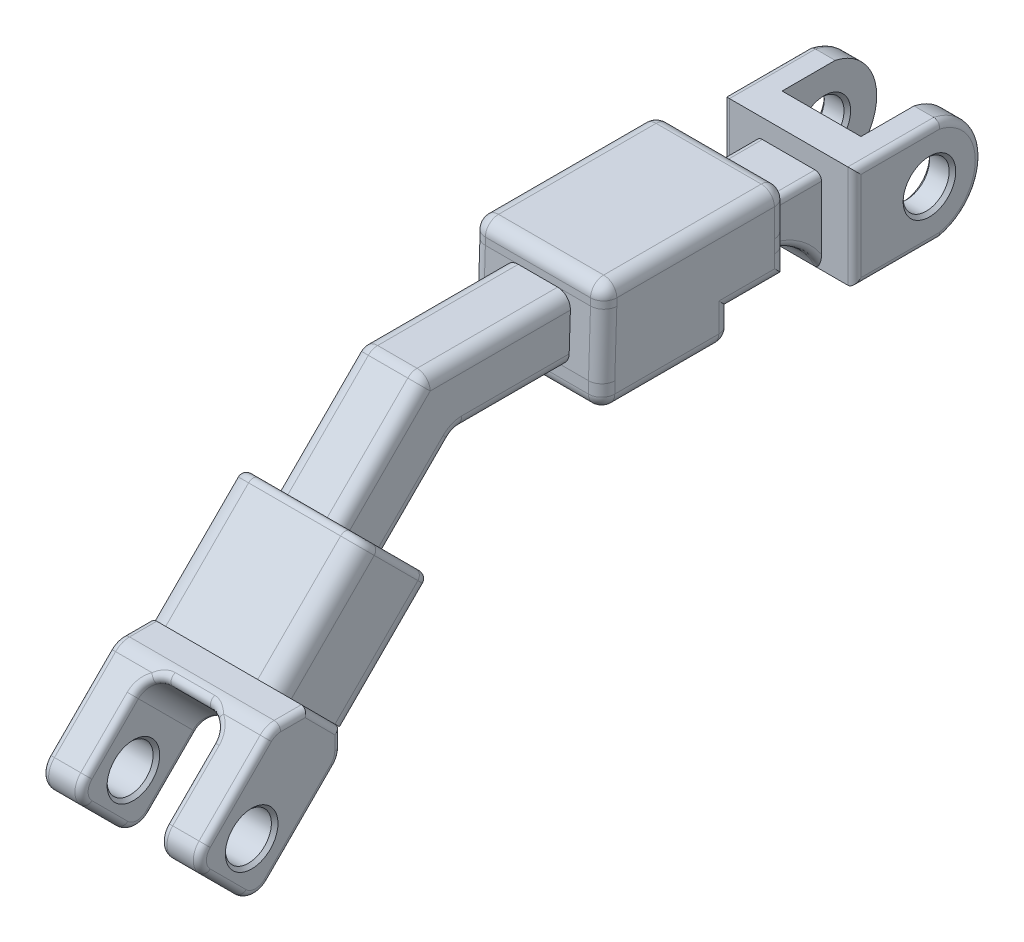
SolidWorks part; units mm, degrees
material "ABS"
ref_plane "Alzado" through (0, 0, 0) normal (0, 0, 1) x (1, 0, 0)
ref_plane "Planta" through (0, 0, 0) normal (0, 1, 0) x (1, 0, 0)
ref_plane "Vista lateral" through (0, 0, 0) normal (1, 0, 0) x (0, 0, -1)
sketch "Croquis4" plane through (0, 0, 0) normal (1, 0, 0) x (0, 0, -1)
  line L0 (294.0556, 267.4264) -> (188.8081, 235.4428) construction
  dimension "D1" = 110
sketch "Croquis5" plane through (0, 0, 0) normal (1, 0, 0) x (0, 0, -1)
  line L0 (179.8347, 236.2643) -> (192.1387, 248.5683)
  line L1 (205.7706, 240.3199) -> (219.087, 253.6362)
  line L2 (219.087, 253.6362) -> (216.6986, 256.0246)
  line L3 (216.6986, 256.0246) -> (227.0958, 266.4218)
  line L4 (227.0958, 266.4218) -> (244.2135, 266.4218)
  line L5 (244.2135, 266.4218) -> (244.2135, 262.6525)
  line L6 (244.2135, 262.6525) -> (264.0386, 262.6525)
  line L7 (264.0386, 262.6525) -> (264.0386, 266.9967)
  line L8 (264.0386, 266.9967) -> (272.5471, 266.9967)
  line L9 (272.5471, 266.9967) -> (272.5471, 271.0085)
  line L10 (272.503, 279.1821) -> (244.5251, 279.1821)
  line L11 (244.5251, 279.1821) -> (244.5251, 276.0953)
  line L12 (244.5251, 276.0953) -> (222.3028, 276.0953)
  line L13 (222.3028, 276.0953) -> (209.4654, 263.2578)
  line L14 (209.4654, 263.2578) -> (208.203, 264.5202)
  line L15 (208.203, 264.5202) -> (194.8866, 251.2039)
  line L16 (272.5471, 271.0085) -> (282.6775, 271.0085)
  line L17 (282.6775, 271.0085) -> (282.6775, 260.2579)
  line L18 (282.6775, 260.2579) -> (295.7469, 260.2579)
  line L19 (295.7469, 275.8569) -> (282.6775, 275.8569)
  line L20 (282.6775, 275.8569) -> (282.6775, 272.9671)
  line L21 (282.6775, 272.9671) -> (272.503, 272.9671)
  line L22 (272.503, 272.9671) -> (272.503, 279.1821)
  line L23 (179.8347, 236.2643) -> (189.5274, 226.5716)
  line L24 (189.5274, 226.5716) -> (202.6077, 239.652)
  line L25 (202.6077, 239.652) -> (202.6077, 243.4632)
  line L26 (202.6077, 243.4632) -> (205.7706, 240.3199)
  line L27 (192.1387, 248.5683) -> (197.5222, 248.5683)
  line L28 (197.5222, 248.5683) -> (194.8866, 251.2039)
  arc A0 (295.7469, 260.2579) -> (295.7469, 275.8569) centre (294.0991, 268.0574) ccw
extrude "Saliente-Extruir1" add sketch "Croquis5" along normal blind 20
sketch "Croquis6" plane through (0, 28.2148, 28.2148) normal (0, 0.7071, 0.7071) x (1, 0, 0)
  line L0 (20, 294.2264) -> (0, 294.2264) construction
  line L1 (4, 294.2264) -> (16, 294.2264)
  line L2 (4, 294.2264) -> (4, 310.2264)
  line L3 (4, 310.2264) -> (16, 310.2264)
  line L4 (16, 294.2264) -> (16, 310.2264)
  line L5 (10, 310.2264) -> (10, 294.2264) construction
  line L6 (0, 311.6269) -> (0, 294.2264) construction
  line L7 (20, 311.6269) -> (20, 294.2264) construction
  dimension "D1" = 12
  dimension "D2" = 16
extrude "Cortar-Extruir1" cut sketch "Croquis6" against normal through all
fillet "Redondeo1" radius 3 6 edges at (10, 239.652, -202.6077) (10, 248.5683, -192.1387) (18, 236.2643, -179.8347) (2, 236.2643, -179.8347) (2, 226.5716, -189.5274) (18, 226.5716, -189.5274)
sketch "Croquis7" plane through (20, 0, 0) normal (1, 0, 0) x (0, 0, -1)
  line L0 (209.4654, 263.2578) -> (216.6986, 256.0246)
  line L1 (216.6986, 256.0246) -> (227.0958, 266.4218)
  line L2 (227.0958, 266.4218) -> (244.2135, 266.4218)
  line L3 (244.2135, 266.4218) -> (244.5251, 276.0953)
  line L4 (244.5251, 276.0953) -> (222.3028, 276.0953)
  line L5 (222.3028, 276.0953) -> (209.4654, 263.2578)
extrude "Cortar-Extruir2" cut sketch "Croquis7" against normal blind 5
sketch "Croquis8" plane through (0, 0, 0) normal (-1, 0, 0) x (0, 0, 1)
  line L0 (-244.5251, 276.0953) -> (-244.2135, 266.4218)
  line L1 (-244.2135, 266.4218) -> (-227.0958, 266.4218)
  line L2 (-227.0958, 266.4218) -> (-216.6986, 256.0246)
  line L3 (-216.6986, 256.0246) -> (-209.4654, 263.2578)
  line L4 (-209.4654, 263.2578) -> (-222.3028, 276.0953)
  line L5 (-222.3028, 276.0953) -> (-244.5251, 276.0953)
extrude "Cortar-Extruir3" cut sketch "Croquis8" against normal blind 5
sketch "Croquis9" plane through (20, 0, 0) normal (1, 0, 0) x (0, 0, -1)
  line L0 (272.503, 272.9671) -> (272.5471, 271.0085)
  line L1 (272.5471, 271.0085) -> (282.6775, 271.0085)
  line L2 (282.6775, 271.0085) -> (282.6775, 272.9671)
  line L3 (282.6775, 275.8569) -> (282.6775, 272.9671) construction
  line L4 (282.6775, 272.9671) -> (272.503, 272.9671) construction
  line L5 (282.6775, 272.9671) -> (272.503, 272.9671)
extrude "Cortar-Extruir4" cut sketch "Croquis9" against normal blind 5
sketch "Croquis10" plane through (0, 0, 0) normal (-1, 0, 0) x (0, 0, 1)
  line L0 (-282.6775, 272.9671) -> (-282.6775, 271.0085)
  line L1 (-282.6775, 271.0085) -> (-272.5471, 271.0085)
  line L2 (-272.5471, 271.0085) -> (-272.503, 272.9671)
  line L3 (-272.503, 272.9671) -> (-282.6775, 272.9671)
extrude "Cortar-Extruir5" cut sketch "Croquis10" against normal blind 5
sketch "Croquis11" plane through (0, 275.8569, 0) normal (0, 1, 0) x (1, 0, 0)
  line L0 (10, 287.6775) -> (10, 308.2863) construction
  line L1 (4, 308.2863) -> (16, 308.2863)
  line L2 (4, 308.2863) -> (4, 287.6775)
  line L3 (4, 287.6775) -> (16, 287.6775)
  line L4 (16, 308.2863) -> (16, 287.6775)
  line L5 (0, 295.7469) -> (0, 282.6775) construction
  line L6 (20, 295.7469) -> (20, 282.6775) construction
  line L7 (20, 282.6775) -> (0, 282.6775) construction
  dimension "D1" = 12
  dimension "D2" = 5
  dimension "D3" = 20.6088
extrude "Cortar-Extruir6" cut sketch "Croquis11" against normal through all
fillet "Redondeo2" radius 3 2 edges at (16, 242.7317, -195.9948) (4, 242.7317, -195.9948)
sketch "Croquis12" plane through (15, 0, 0) normal (1, 0, 0) x (0, 0, -1)
  line L2 (272.5471, 266.9967) -> (272.5471, 271.0085)
  line L3 (272.5471, 271.0085) -> (282.6775, 271.0085)
  line L4 (282.6775, 271.0085) -> (282.6775, 260.2579)
  arc A1 (272.5471, 266.9967) -> (282.6775, 260.2579) centre (272.143, 255.4052) cw
  dimension "D1" = 11.5985
extrude "Saliente-Extruir2" add sketch "Croquis12" against normal up to surface (10 mm away) up to face at (5, 271.9878, -277.6013)
fillet "Redondeo4" radius 3 4 edges at (0, 257.8621, -201.5448) (0, 246.9781, -212.4288) (20, 246.9781, -212.4288) (20, 257.8621, -201.5448)
fillet "Redondeo5" radius 2 10 edges at (5, 266.4218, -235.6546) (10, 266.4218, -227.0958) (5, 261.2232, -221.8972) (5, 276.0953, -233.4139) (10, 276.0953, -222.3028) (5, 269.6766, -215.8841) (15, 276.0953, -233.4139) (15, 269.6766, -215.8841) (15, 266.4218, -235.6546) (15, 261.2232, -221.8972)
fillet "Redondeo6" radius 2 24 edges at (10, 279.1821, -272.503) (10, 279.1821, -244.5251) (20, 269.0026, -272.5471) (20, 266.9967, -268.2928) (20, 264.8246, -264.0386) (20, 264.5371, -244.2135) (20, 271.2585, -244.3693) (20, 277.6387, -244.5251) (20, 279.1821, -258.514) (20, 276.0746, -272.503) (20, 271.9878, -272.525) (0, 279.1821, -258.514) (0, 277.6387, -244.5251) (0, 271.2585, -244.3693) (0, 264.5371, -244.2135) (0, 264.8246, -264.0386) (0, 266.9967, -268.2928) (0, 269.0026, -272.5471) (0, 271.9878, -272.525) (0, 276.0746, -272.503) (10, 262.6525, -244.2135) (20, 262.6525, -254.126) (10, 262.6525, -264.0386) (0, 262.6525, -254.126)
sketch "Croquis13" plane through (20, 0, 0) normal (1, 0, 0) x (0, 0, -1)
  line L0 (197.5222, 248.5683) -> (193.3814, 248.5683) construction
  line L1 (191.2601, 247.6896) -> (181.956, 238.3856) construction
  line L2 (181.956, 234.143) -> (187.406, 228.693) construction
  line L3 (191.6487, 228.693) -> (201.729, 238.7733) construction
  line L4 (202.6077, 240.8946) -> (202.6077, 243.4632) construction
  line L5 (197.5222, 248.5683) -> (193.3814, 248.5683)
  line L6 (191.2601, 247.6896) -> (181.956, 238.3856)
  line L7 (181.956, 234.143) -> (187.406, 228.693)
  line L8 (191.6487, 228.693) -> (201.729, 238.7733)
  line L9 (202.6077, 240.8946) -> (202.6077, 243.4632)
  line L10 (202.6077, 243.4632) -> (197.5222, 248.5683)
  arc A0 (193.3814, 248.5683) -> (191.2601, 247.6896) centre (193.3814, 245.5683) ccw construction
  arc A1 (181.956, 238.3856) -> (181.956, 234.143) centre (184.0774, 236.2643) ccw construction
  arc A2 (187.406, 228.693) -> (191.6487, 228.693) centre (189.5274, 230.8143) ccw construction
  arc A3 (201.729, 238.7733) -> (202.6077, 240.8946) centre (199.6077, 240.8946) ccw construction
  arc A4 (193.3814, 248.5683) -> (191.2601, 247.6896) centre (193.3814, 245.5683) ccw
  arc A5 (181.956, 238.3856) -> (181.956, 234.143) centre (184.0774, 236.2643) ccw
  arc A6 (187.406, 228.693) -> (191.6487, 228.693) centre (189.5274, 230.8143) ccw
  arc A7 (201.729, 238.7733) -> (202.6077, 240.8946) centre (199.6077, 240.8946) ccw
extrude "Saliente-Extruir3" add sketch "Croquis13" along normal blind 2
sketch "Croquis14" plane through (0, 0, 0) normal (-1, 0, 0) x (0, 0, 1)
  line L0 (-197.5222, 248.5683) -> (-202.6077, 243.4632)
  line L7 (-210.3243, 262.3989) -> (-216.9656, 255.7576)
  line L8 (-202.6077, 243.4632) -> (-202.6077, 240.8946)
  line L9 (-202.6077, 243.4632) -> (-202.6077, 240.8946)
  line L10 (-197.5222, 248.5683) -> (-197.0079, 249.0825)
  line L11 (-197.0079, 249.0825) -> (-210.3243, 262.3989)
  line L13 (-216.9656, 255.7576) -> (-203.6427, 242.4346)
  line L14 (-203.6427, 242.4346) -> (-202.6077, 243.4632)
  line L18 (-201.729, 238.7733) -> (-191.6487, 228.693)
  line L19 (-201.729, 238.7733) -> (-191.6487, 228.693)
  line L20 (-187.406, 228.693) -> (-181.956, 234.143)
  line L21 (-187.406, 228.693) -> (-181.956, 234.143)
  line L22 (-181.956, 238.3856) -> (-191.2601, 247.6896)
  line L23 (-181.956, 238.3856) -> (-191.2601, 247.6896)
  line L24 (-193.3814, 248.5683) -> (-197.5222, 248.5683)
  line L25 (-193.3814, 248.5683) -> (-197.5222, 248.5683)
  arc A4 (-202.6077, 240.8946) -> (-201.729, 238.7733) centre (-199.6077, 240.8946) ccw
  arc A5 (-202.6077, 240.8946) -> (-201.729, 238.7733) centre (-199.6077, 240.8946) ccw
  arc A6 (-191.6487, 228.693) -> (-187.406, 228.693) centre (-189.5274, 230.8143) ccw
  arc A7 (-191.6487, 228.693) -> (-187.406, 228.693) centre (-189.5274, 230.8143) ccw
  arc A8 (-181.956, 234.143) -> (-181.956, 238.3856) centre (-184.0774, 236.2643) ccw
  arc A9 (-181.956, 234.143) -> (-181.956, 238.3856) centre (-184.0774, 236.2643) ccw
  arc A10 (-191.2601, 247.6896) -> (-193.3814, 248.5683) centre (-193.3814, 245.5683) ccw
  arc A11 (-191.2601, 247.6896) -> (-193.3814, 248.5683) centre (-193.3814, 245.5683) ccw
  dimension "D1" = 0
extrude "Saliente-Extruir4" add sketch "Croquis14" along normal blind 2
fillet "Redondeo7" radius 1 20 edges at (-2, 248.3399, -192.2333) (-2, 243.0376, -186.608) (-2, 236.2643, -181.0774) (-2, 231.418, -184.681) (-2, 227.8143, -189.5274) (-2, 233.7331, -196.6889) (-2, 239.7466, -202.3794) (-2, 242.1789, -202.6077) (-2, 246.0157, -200.065) (-2, 248.5683, -195.4518) (22, 242.1789, -202.6077) (22, 239.7466, -202.3794) (22, 233.7331, -196.6889) (22, 227.8143, -189.5274) (22, 231.418, -184.681) (22, 236.2643, -181.0774) (22, 243.0376, -186.608) (22, 248.3399, -192.2333) (22, 248.5683, -195.4518) (22, 246.0157, -200.065)
fillet "Redondeo8" radius 1 4 edges at (15, 272.9671, -277.5903) (5, 272.9671, -277.5903) (5, 265.0623, -278.5668) (15, 265.0623, -278.5668)
fillet "Redondeo9" radius 1 8 edges at (0, 268.0574, -302.0708) (0, 275.8569, -289.2122) (0, 268.0574, -282.6775) (0, 260.2579, -289.2122) (20, 268.0574, -302.0708) (20, 260.2579, -289.2122) (20, 268.0574, -282.6775) (20, 275.8569, -289.2122)
fillet "Redondeo11" radius 1 16 edges at (4.8787, 246.9567, -190.5271) (10, 247.578, -191.1484) (15.1213, 246.9567, -190.5271) (16, 241.9211, -185.4916) (16, 236.2643, -181.0774) (16, 231.418, -184.681) (16, 227.8143, -189.5274) (16, 232.2285, -195.1842) (15.1213, 237.264, -200.2198) (10, 237.8853, -200.8411) (4.8787, 237.264, -200.2198) (4, 232.2285, -195.1842) (4, 227.8143, -189.5274) (4, 231.418, -184.681) (4, 236.2643, -181.0774) (4, 241.9211, -185.4916)
fillet "Redondeo13" radius 1 8 edges at (19.1213, 263.8989, -208.8243) (20, 259.0782, -213.645) (19.1213, 254.2576, -218.4656) (10, 253.6362, -219.087) (0.8787, 254.2576, -218.4656) (0, 259.0782, -213.645) (0.8787, 263.8989, -208.8243) (10, 264.5202, -208.203)
sketch "Croquis16" plane through (22, 0, 0) normal (1, 0, 0) x (0, 0, -1)
  line L0 (185.3882, 232.1251) -> (195.4875, 242.2245) construction
  line L1 (182.6632, 234.8501) -> (188.1132, 229.4001) construction
  line L2 (191.9672, 246.9825) -> (182.6632, 237.6785) construction
  circle A0 centre (188.9652, 235.7022) radius 3.5
  circle A1 centre (294.0991, 268.0574) radius 3.5
  arc A2 (295.6388, 261.2579) -> (295.6388, 274.8569) centre (294.0991, 268.0574) ccw construction
  dimension "D2" = 7
  dimension "D1" = 110
extrude "Cortar-Extruir7" cut sketch "Croquis16" against normal through all
chamfer "Chaflán1" distance 0.5 angle 45 8 edges at (0, 268.0574, -297.5991) (4, 268.0574, -290.5991) (16, 268.0574, -297.5991) (20, 268.0574, -297.5991) (16, 239.2022, -188.9652) (4, 235.7022, -185.4652) (-2, 235.7022, -192.4652) (22, 235.7022, -192.4652)
